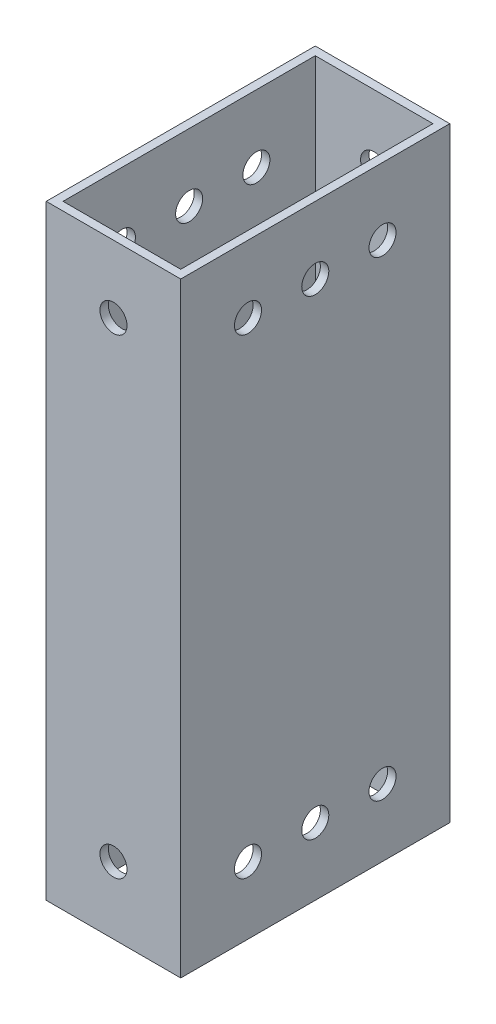
SolidWorks part; units mm, degrees
material "6061-T6 (SS)"
ref_plane "Front" through (0, 0, 0) normal (0, 0, 1) x (1, 0, 0)
ref_plane "Top" through (0, 0, 0) normal (0, 1, 0) x (1, 0, 0)
ref_plane "Right" through (0, 0, 0) normal (1, 0, 0) x (0, 0, -1)
sketch "Sketch1" plane through (0, 0, 0) normal (0, 1, 0) x (1, 0, 0)
  line L1 (12.7, 25.4) -> (-12.7, 25.4)
  line L2 (12.7, 25.4) -> (12.7, -25.4)
  line L3 (12.7, -25.4) -> (-12.7, -25.4)
  line L4 (-12.7, 25.4) -> (-12.7, -25.4)
  line L5 (12.7, 25.4) -> (-12.7, -25.4) construction
  line L6 (12.7, -25.4) -> (-12.7, 25.4) construction
  point P0 (0, 0)
  dimension "D1" = 25.4
  dimension "D2" = 50.8
extrude "Extrude-Thin1" add sketch "Sketch1" along normal up to surface (114.3 mm away) thin thin type one direction reverse wall 1.5875
sketch "Sketch4" plane through (-12.7, 0, 0) normal (-1, 0, 0) x (0, 0, 1)
  line L0 (-12.7, 12.7) -> (12.7, 12.7) construction
  line L3 (-12.7, 101.6) -> (12.7, 101.6) construction
  line L5 (-25.4, 0) -> (25.4, 0) construction
  line L6 (-25.4, 114.3) -> (25.4, 114.3) construction
  point P0 (-12.7, 101.6)
  point P2 (0, 101.6)
  point P4 (12.7, 101.6)
  point P6 (-12.7, 12.7)
  point P8 (0, 12.7)
  point P10 (12.7, 12.7)
  dimension "D1" = 12.7
  dimension "D2" = 12.7
  dimension "D3" = 12.7
  dimension "D4" = 12.7
hole_wizard "#10 Clearance Hole1" positions "Sketch4" profile "Sketch3" hole size "#10" standard "ANSI Inch" end condition through all
sketch "Sketch3" plane through (-12.7, 101.6, -12.7) normal (0, 1, 0) x (0, 0, 1)
  line L0 (0, 0) -> (0, 25.4)
  line L1 (0, 25.4) -> (2.5527, 25.4)
  line L2 (2.5527, 25.4) -> (2.5527, 0)
  line L5 (2.5527, 0) -> (0, 0)
  line L11 (0, -6.35) -> (0, 107.95) construction
  dimension "Thru Hole Dia." = 5.1054
  dimension "Thru Hole Depth" = 25.4
sketch "Sketch7" plane through (0, 0, 25.4) normal (0, 0, 1) x (1, 0, 0)
  line L0 (-12.7, 0) -> (12.7, 0) construction
  line L1 (-12.7, 114.3) -> (12.7, 114.3) construction
  point P0 (0, 12.7)
  point P2 (0, 101.6)
  dimension "D1" = 12.7
  dimension "D2" = 12.7
hole_wizard "#10 Clearance Hole2" positions "Sketch7" profile "Sketch6" hole size "#10" standard "ANSI Inch" end condition through all
sketch "Sketch6" plane through (0, 12.7, 25.4) normal (1, 0, 0) x (0, -1, 0)
  line L0 (0, 0) -> (0, 50.8)
  line L1 (0, 50.8) -> (2.5527, 50.8)
  line L2 (2.5527, 50.8) -> (2.5527, 0)
  line L5 (2.5527, 0) -> (0, 0)
  line L11 (0, -6.35) -> (0, 107.95) construction
  dimension "Thru Hole Dia." = 5.1054
  dimension "Thru Hole Depth" = 50.8
